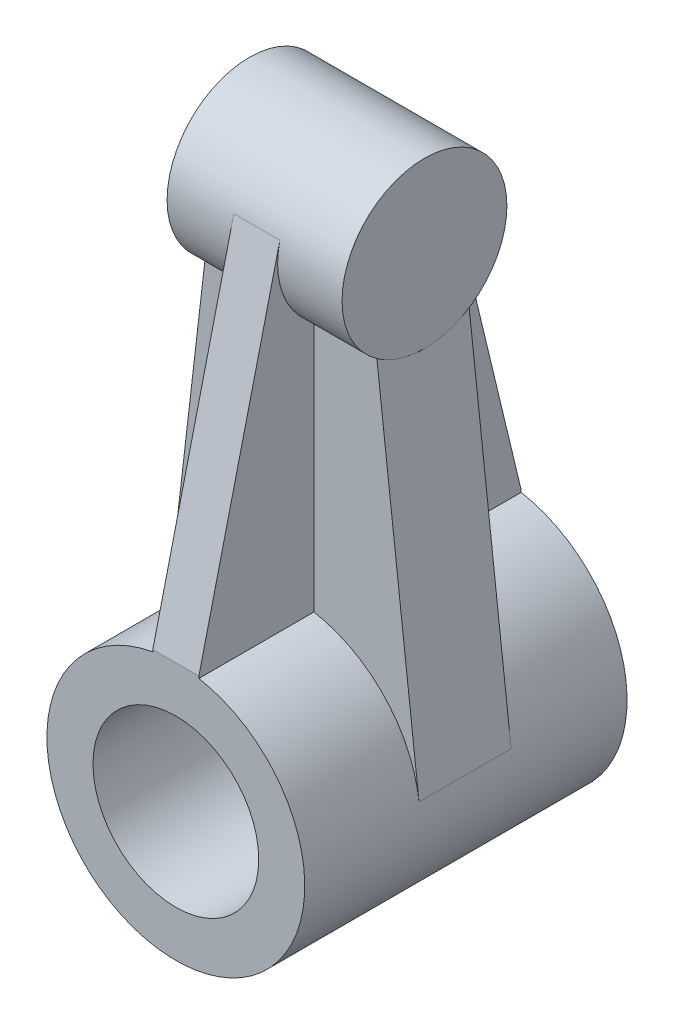
SolidWorks part; units mm, degrees
ref_plane "Front Plane" through (0, 0, 0) normal (0, 0, 1) x (1, 0, 0)
ref_plane "Top Plane" through (0, 0, 0) normal (0, 1, 0) x (1, 0, 0)
ref_plane "Right Plane" through (0, 0, 0) normal (1, 0, 0) x (0, 0, -1)
sketch "Sketch1" plane through (0, 0, 0) normal (0, 0, 1) x (1, 0, 0)
  circle A0 centre (0, 0) radius 14
  circle A1 centre (0, 0) radius 9
  dimension "D1" = 18
  dimension "D2" = 28
extrude "Boss-Extrude1" add sketch "Sketch1" along normal blind 35
sketch "Sketch3" plane through (0, 0, 0) normal (1, 0, 0) x (0, 0, -1)
  line L0 (-41.7574, 0) -> (13.6005, 0) construction
  line L1 (-17.5, 14) -> (-17.5, -17.6185) construction
  line L2 (0, 14) -> (-35, 14) construction
  line L3 (-17.5, 14) -> (-17.5, 48.4964) construction
  line L4 (-35, 11.9524) -> (-35, 14)
  line L5 (-35, 14) -> (-35, -14) construction
  line L6 (-35, 14) -> (-26.2026, 50.5888)
  line L7 (0, 14) -> (-8.7974, 50.5888)
  line L8 (-35, 14) -> (0, 14)
  circle A0 centre (-17.5, 48.4964) radius 8.9506
  circle A1 centre (-17.5, 48.4964) radius 6.6081
extrude "Boss-Extrude2" add sketch "Sketch3" along normal mid plane 19 separate body contours A0
extrude "Boss-Extrude3" add sketch "Sketch3<3>" along normal mid plane 5 contours A0 L6 L8 L7 region at (0, 27.0621, 17.5)
sketch "Sketch3<3>" plane through (0, 0, 0) normal (1, 0, 0) x (0, 0, -1) same geometry as "Sketch3"
sketch "Sketch7" plane through (0, 14, 0) normal (0, -1, 0) x (1, 0, 0)
  line L4 (-2.5, 35) -> (-2.5, 0)
  line L5 (-2.5, 0) -> (2.5, 0)
  line L6 (2.5, 0) -> (2.5, 35)
  line L7 (2.5, 35) -> (-2.5, 35)
  line L8 (-2.5, 35) -> (-2.5, 0)
  line L9 (-2.5, 0) -> (2.5, 0)
  line L10 (2.5, 0) -> (2.5, 35)
  line L11 (2.5, 35) -> (-2.5, 35)
  dimension "D1" = 0
extrude "Boss-Extrude5" add sketch "Sketch7" along normal up to next (5 mm away)
ref_plane "Plane1" through (0, 0, 17.5) normal (0, 0, -1) x (-1, 0, 0)
sketch "Sketch6" plane through (0, 0, 17.5) normal (0, 0, -1) x (-1, 0, 0)
  line L0 (-9.5, 39.5458) -> (-13.9065, 1.6156)
  line L1 (0, 0) -> (0, 71.1324) construction
  circle A0 centre (0, 0) radius 14 construction
rib "Rib12" sketch "Sketch6" sketch "Sketch6" thickness 10 extrusion direction parallel to sketch draft on no parameters "D1"=10
mirror "Mirror1" about plane through (0, 0, 0) normal (1, 0, 0) of "Rib12"
